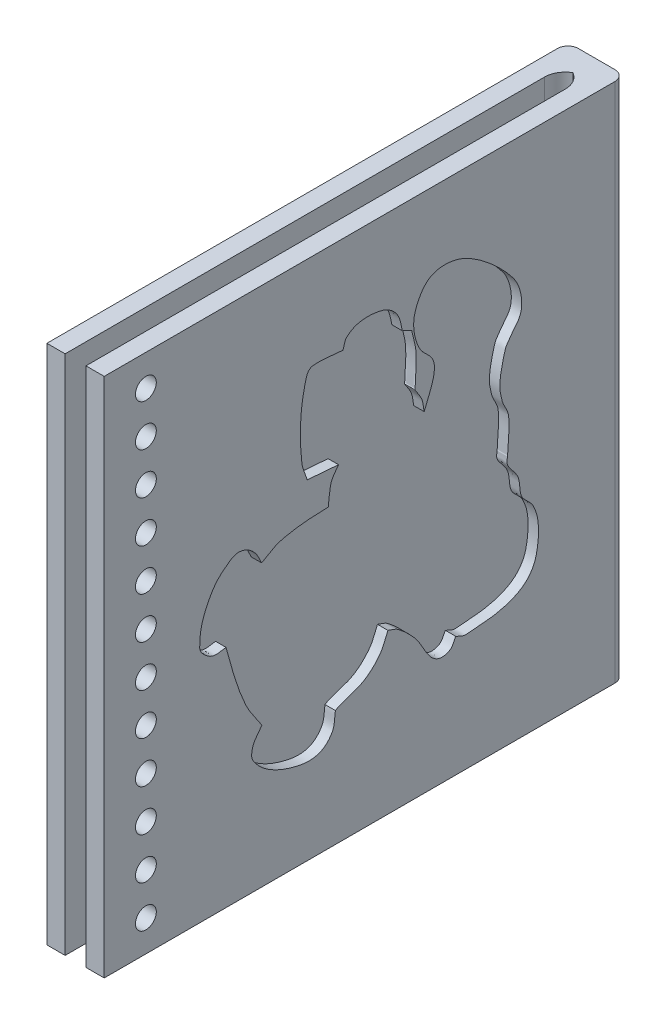
SolidWorks part; units mm, degrees
ref_plane "Front Plane" through (0, 0, 0) normal (0, 0, 1) x (1, 0, 0)
ref_plane "Top Plane" through (0, 0, 0) normal (0, 1, 0) x (1, 0, 0)
ref_plane "Right Plane" through (0, 0, 0) normal (1, 0, 0) x (0, 0, -1)
sketch "Sketch1" plane through (0, 0, 0) normal (0, 0, 1) x (1, 0, 0)
  line L1 (1.375, -12.5) -> (-1.375, -12.5)
  line L2 (1.375, -12.5) -> (1.375, 12.5)
  line L3 (1.375, 12.5) -> (-1.375, 12.5)
  line L4 (-1.375, -12.5) -> (-1.375, 12.5)
  line L5 (1.375, -12.5) -> (-1.375, 12.5) construction
  line L6 (1.375, 12.5) -> (-1.375, -12.5) construction
  point P0 (0, 0)
  dimension "D1" = 2.75
  dimension "D2" = 25
extrude "Boss-Extrude1" add sketch "Sketch1" along normal blind 25
sketch "Sketch2" plane through (0, 0, 25) normal (0, 0, 1) x (1, 0, 0)
  line L0 (1.375, 12.5) -> (-1.375, 12.5) construction
  line L1 (0.5, -12.5) -> (-0.5, -12.5)
  line L2 (0.5, -12.5) -> (0.5, 12.5)
  line L3 (0.5, 12.5) -> (-0.5, 12.5)
  line L4 (-0.5, -12.5) -> (-0.5, 12.5)
  line L5 (0.5, -12.5) -> (-0.5, 12.5) construction
  line L6 (0.5, 12.5) -> (-0.5, -12.5) construction
  point P0 (0, 0)
  dimension "D1" = 1
extrude "Cut-Extrude1" cut sketch "Sketch2" against normal blind 24
fillet "Fillet2" radius 1 2 edges at (0.5, 0, 1) (-0.5, 0, 1)
sketch "Sketch6" plane through (0, 0, 0) normal (1, 0, 0) x (0, 0, -1)
  line L0 (-13.7566, 3.2081) -> (-15.2566, 3.3281)
  line L1 (-10.6966, 7.2431) -> (-10.2466, 7.0331)
  spline S0 degree 3 poles (-19.1566, -1.6819) (-19.3616, -1.6969) (-19.5715, -1.7741) (-19.7716, -1.7269) (-19.9511, -1.6845) (-20.1062, -1.5573) (-20.2366, -1.4269) (-20.3283, -1.3352) (-20.4124, -1.2115) (-20.4166, -1.0819) (-20.428, -0.7292) (-20.3898, -0.3678) (-20.2816, -0.0319) (-20.1465, 0.3874) (-19.9535, 0.7952) (-19.6966, 1.1531) (-19.5005, 1.4263) (-19.2243, 1.6383) (-18.9466, 1.8281) (-18.8213, 1.9138) (-18.6632, 1.9704) (-18.5116, 1.9631) (-18.3362, 1.9546) (-18.1565, 1.8892) (-18.0166, 1.7831) (-17.6811, 1.5287) (-17.6019, 1.3009) (-17.4466, 0.9731) knots 0 0 0 0 1 1 1 2 2 2 3 3 3 4 4 4 5 5 5 6 6 6 7 7 7 8 8 8 9 9 9 9
  spline S1 degree 3 poles (-17.4466, 0.9731) (-17.1416, 1.1281) (-16.8621, 1.3498) (-16.5316, 1.4381) (-15.7927, 1.6354) (-15.0161, 1.6724) (-14.2516, 1.6931) knots 0 0 0 0 1 1 1 2 2 2 2
  spline S2 degree 3 poles (-14.2516, 1.6931) (-14.2016, 2.0181) (-14.2037, 2.3555) (-14.1016, 2.6681) (-14.0353, 2.8711) (-13.8716, 3.0281) (-13.7566, 3.2081) knots 0 0 0 0 1 1 1 2 2 2 2
  spline S3 degree 3 poles (-15.2566, 3.3281) (-15.3416, 3.5981) (-15.4781, 3.857) (-15.5116, 4.1381) (-15.5839, 4.7441) (-15.6106, 5.359) (-15.5716, 5.9681) (-15.5353, 6.5349) (-15.4448, 7.1026) (-15.2866, 7.6481) (-15.2492, 7.7771) (-15.135, 7.917) (-15.0016, 7.9331) (-14.5195, 7.9913) (-14.0316, 7.8831) (-13.5466, 7.8581) knots 0 0 0 0 1 1 1 2 2 2 3 3 3 4 4 4 5 5 5 5
  spline S4 degree 3 poles (-13.5466, 7.8581) (-13.4816, 8.0131) (-13.4767, 8.2109) (-13.3516, 8.3231) (-13.1667, 8.4888) (-12.9225, 8.6036) (-12.6766, 8.6381) (-12.334, 8.6862) (-11.9743, 8.6577) (-11.6416, 8.5631) (-11.4122, 8.4978) (-11.1979, 8.3533) (-11.0416, 8.1731) (-10.8045, 7.8998) (-10.762, 7.5702) (-10.6966, 7.2431) knots 0 0 0 0 1 1 1 2 2 2 3 3 3 4 4 4 5 5 5 5
  spline S5 degree 3 poles (-10.2466, 7.0331) (-10.1766, 6.6931) (-10.0595, 6.3595) (-10.0366, 6.0131) (-10.0042, 5.5239) (-10.0622, 5.0329) (-10.0816, 4.5431) (-10.0822, 4.5273) (-10.1039, 4.5121) (-10.0966, 4.4981) (-9.9965, 4.3075) (-9.8456, 4.1433) (-9.7666, 3.9431) (-9.6935, 3.7579) (-9.6866, 3.5531) (-9.6466, 3.3581) knots 0 0 0 0 1 1 1 2 2 2 3 3 3 4 4 4 5 5 5 5
  spline S6 degree 3 poles (-9.6466, 3.3581) (-9.4966, 3.7681) (-9.2885, 4.1613) (-9.1966, 4.5881) (-9.146, 4.8229) (-9.129, 5.0886) (-9.2266, 5.3081) (-9.3608, 5.61) (-9.7007, 5.7818) (-9.8566, 6.0731) (-10.0118, 6.3632) (-10.1086, 6.6907) (-10.1416, 7.0181) (-10.1699, 7.2988) (-10.139, 7.5951) (-10.0366, 7.8581) (-9.9133, 8.1747) (-9.7429, 8.4959) (-9.4816, 8.7131) (-9.2713, 8.888) (-8.975, 8.9611) (-8.7016, 8.9681) (-8.3644, 8.9767) (-8.0173, 8.9006) (-7.7116, 8.7581) (-7.2641, 8.5495) (-6.8571, 8.2536) (-6.4816, 7.9331) (-6.0673, 7.5795) (-5.6797, 7.1866) (-5.3566, 6.7481) (-5.1825, 6.5118) (-5.0697, 6.2258) (-5.0116, 5.9381) (-4.9572, 5.6685) (-4.9381, 5.3735) (-5.0266, 5.1131) (-5.1261, 4.8202) (-5.3824, 4.607) (-5.5516, 4.3481) (-5.6276, 4.2318) (-5.7233, 4.1216) (-5.7616, 3.9881) (-5.8798, 3.5762) (-5.9852, 3.1555) (-6.0166, 2.7281) (-6.0358, 2.4665) (-5.9792, 2.2016) (-5.9116, 1.9481) (-5.8382, 1.6727) (-5.6285, 1.4364) (-5.5966, 1.1531) (-5.5368, 0.6212) (-5.6223, 0.083) (-5.6416, -0.4519) (-5.6423, -0.4725) (-5.6566, -0.4913) (-5.6566, -0.5119) (-5.6566, -0.632) (-5.6923, -0.763) (-5.6416, -0.8719) (-5.5169, -1.1397) (-5.2593, -1.3339) (-5.1466, -1.6069) (-5.0298, -1.8897) (-5.0958, -2.2296) (-4.9666, -2.5069) (-4.8482, -2.7611) (-4.5559, -2.9031) (-4.4266, -3.1519) (-4.285, -3.4243) (-4.1929, -3.7306) (-4.1716, -4.0369) (-4.1421, -4.4623) (-4.1746, -4.8978) (-4.2766, -5.3119) (-4.3429, -5.5812) (-4.4795, -5.8421) (-4.6666, -6.0469) (-4.8611, -6.2599) (-5.1189, -6.4194) (-5.3866, -6.5269) (-5.7636, -6.6783) (-6.1667, -6.7784) (-6.5716, -6.8119) (-7.79, -6.9129) (-7.6522, -6.9766) (-8.1316, -6.7369) knots 0 0 0 0 1 1 1 2 2 2 3 3 3 4 4 4 5 5 5 6 6 6 7 7 7 8 8 8 9 9 9 10 10 10 11 11 11 12 12 12 13 13 13 14 14 14 15 15 15 16 16 16 17 17 17 18 18 18 19 19 19 20 20 20 21 21 21 22 22 22 23 23 23 24 24 24 25 25 25 26 26 26 27 27 27 28 28 28 29 29 29 29
  spline S7 degree 3 poles (-8.1316, -6.7369) (-8.2216, -6.8769) (-8.2644, -7.0627) (-8.4016, -7.1569) (-8.5407, -7.2523) (-8.7309, -7.2935) (-8.8966, -7.2619) (-9.071, -7.2287) (-9.2326, -7.1131) (-9.3466, -6.9769) (-9.6252, -6.644) (-9.7782, -6.2191) (-10.0516, -5.8819) (-10.2966, -5.5798) (-10.5825, -5.3081) (-10.8916, -5.0719) (-11.034, -4.9631) (-11.2216, -4.9319) (-11.3866, -4.8619) knots 0 0 0 0 1 1 1 2 2 2 3 3 3 4 4 4 5 5 5 6 6 6 6
  spline S8 degree 3 poles (-11.3866, -4.8619) (-11.5166, -5.1319) (-11.5949, -5.4336) (-11.7766, -5.6719) (-11.9868, -5.9477) (-12.2436, -6.1995) (-12.5416, -6.3769) (-12.9102, -6.5964) (-13.3442, -6.6803) (-13.7416, -6.8419) (-13.7996, -6.8655) (-13.8516, -6.9019) (-13.9066, -6.9319) knots 0 0 0 0 1 1 1 2 2 2 3 3 3 4 4 4 4
  spline S9 degree 3 poles (-13.9066, -6.9319) (-13.9566, -7.2019) (-13.9264, -7.5001) (-14.0566, -7.7419) (-14.184, -7.9786) (-14.3925, -8.1958) (-14.6416, -8.2969) (-14.9294, -8.4137) (-15.2665, -8.4152) (-15.5716, -8.3569) (-16.0671, -8.2622) (-16.5605, -8.1006) (-16.9966, -7.8469) (-17.3421, -7.646) (-17.6626, -7.3656) (-17.8666, -7.0219) (-17.9713, -6.8456) (-17.9192, -6.6005) (-17.8516, -6.4069) (-17.7683, -6.1686) (-17.5716, -5.9869) (-17.4316, -5.7769) knots 0 0 0 0 1 1 1 2 2 2 3 3 3 4 4 4 5 5 5 6 6 6 7 7 7 7
  spline S10 degree 3 poles (-17.4316, -5.7769) (-17.6866, -5.3769) (-17.9967, -5.0071) (-18.1966, -4.5769) (-18.6251, -3.655) (-18.8946, -2.6643) (-19.1566, -1.6819) knots 0 0 0 0 1 1 1 2 2 2 2
extrude "Cut-Extrude4" cut sketch "Sketch6" against normal blind 0.5 from surface starting at face at (1.375, 0, 12.5)
fillet "Fillet3" radius 0.5 2 edges at (-1.375, 0, 0) (1.375, 0, 0)
sketch "Sketch7" plane through (1.375, 0, 0) normal (1, 0, 0) x (0, 0, -1)
  line L1 (-25, -12.5) -> (-0.5, -12.5) construction
  line L2 (-25, 12.5) -> (-0.5, 12.5) construction
  line L3 (-25, -12.5) -> (-25, 12.5) construction
  circle A0 centre (-23, -11) radius 0.5
  circle A1 centre (-23, -9) radius 0.5
  circle A2 centre (-23, -7) radius 0.5
  circle A3 centre (-23, -5) radius 0.5
  circle A4 centre (-23, -3) radius 0.5
  circle A5 centre (-23, -1) radius 0.5
  circle A6 centre (-23, 1) radius 0.5
  circle A7 centre (-23, 3) radius 0.5
  circle A8 centre (-23, 5) radius 0.5
  circle A9 centre (-23, 7) radius 0.5
  circle A10 centre (-23, 9) radius 0.5
  circle A11 centre (-23, 11) radius 0.5
  dimension "D1" = 1
  dimension "D3" = 1.5
  dimension "D4" = 1.5
  dimension "D5" = 2
  dimension "D2" = 12
extrude "Cut-Extrude5" cut sketch "Sketch7" against normal blind 10
